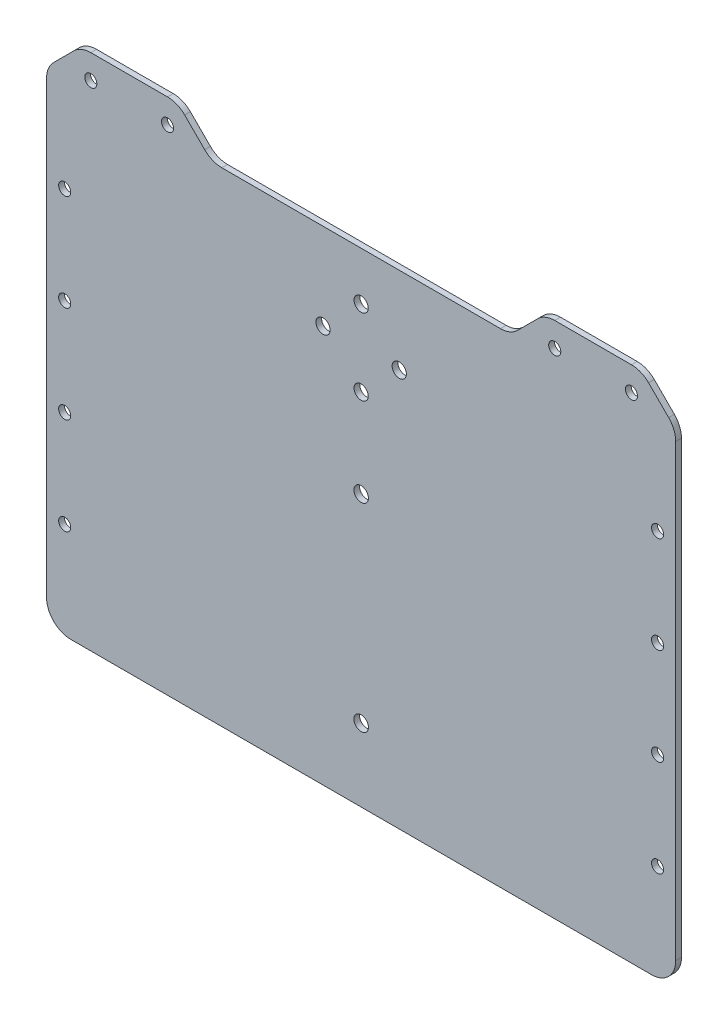
SolidWorks part; units mm, degrees
material "Thornel VCB-20 Carbon Cloth"
ref_plane "Front Plane" through (0, 0, 0) normal (0, 0, 1) x (1, 0, 0)
ref_plane "Top Plane" through (0, 0, 0) normal (0, 1, 0) x (1, 0, 0)
ref_plane "Right Plane" through (0, 0, 0) normal (1, 0, 0) x (0, 0, -1)
sketch "Sketch1" plane through (0, 0, 0) normal (0, 0, 1) x (1, 0, 0)
  line L0 (0, -63.5) -> (0, 63.5) construction
  line L2 (-82.55, 60.8697) -> (-82.55, -57.15)
  line L3 (-76.2, -63.5) -> (76.2, -63.5)
  line L4 (82.55, 60.8697) -> (82.55, -57.15)
  line L5 (-82.55, 63.5) -> (82.55, -63.5) construction
  line L6 (-82.55, -63.5) -> (82.55, 63.5) construction
  line L7 (-80.6901, 65.3599) -> (-75.4296, 70.6204)
  line L8 (-70.9395, 72.4803) -> (-50.8, 72.4803)
  line L9 (-46.3099, 70.6204) -> (-41.0494, 65.3599)
  line L10 (46.3099, 70.6204) -> (41.0494, 65.3599)
  line L11 (70.9395, 72.4803) -> (50.8, 72.4803)
  line L12 (80.6901, 65.3599) -> (75.4296, 70.6204)
  line L13 (-73.5697, 72.4803) -> (-82.55, 72.4803) construction
  line L14 (-82.55, 72.4803) -> (-82.55, 63.5) construction
  line L15 (-36.5592, 63.5) -> (0, 63.5)
  line L16 (0, 63.5) -> (36.5592, 63.5)
  circle A0 centre (-77.7875, -38.1) radius 1.5875
  circle A1 centre (-77.7875, -12.7) radius 1.5875
  circle A2 centre (-77.7875, 12.7) radius 1.5875
  circle A3 centre (-77.7875, 38.1) radius 1.5875
  circle A4 centre (77.7875, 38.1) radius 1.5875
  circle A5 centre (77.7875, 12.7) radius 1.5875
  circle A6 centre (77.7875, -12.7) radius 1.5875
  circle A7 centre (77.7875, -38.1) radius 1.5875
  arc A8 (82.55, 60.8697) -> (80.6901, 65.3599) centre (76.2, 60.8697) ccw
  arc A9 (75.4296, 70.6204) -> (70.9395, 72.4803) centre (70.9395, 66.1303) ccw
  arc A10 (46.3099, 70.6204) -> (50.8, 72.4803) centre (50.8, 66.1303) cw
  arc A11 (41.0494, 65.3599) -> (36.5592, 63.5) centre (36.5592, 69.85) cw
  arc A12 (-36.5592, 63.5) -> (-41.0494, 65.3599) centre (-36.5592, 69.85) cw
  arc A13 (-46.3099, 70.6204) -> (-50.8, 72.4803) centre (-50.8, 66.1303) ccw
  arc A14 (-70.9395, 72.4803) -> (-75.4296, 70.6204) centre (-70.9395, 66.1303) ccw
  arc A15 (-82.55, 60.8697) -> (-80.6901, 65.3599) centre (-76.2, 60.8697) cw
  arc A16 (76.2, -63.5) -> (82.55, -57.15) centre (76.2, -57.15) ccw
  arc A17 (-76.2, -63.5) -> (-82.55, -57.15) centre (-76.2, -57.15) cw
  circle A18 centre (-70.9395, 66.1303) radius 1.5875
  circle A19 centre (-50.8, 66.1303) radius 1.5875
  circle A20 centre (50.8, 66.1303) radius 1.5875
  circle A21 centre (70.9395, 66.1303) radius 1.5875
  point P0 (0, 0)
  point P36 (73.5697, 72.4803)
  point P39 (48.1697, 72.4803)
  point P42 (39.1895, 63.5)
  point P45 (-39.1895, 63.5)
  point P48 (-48.1697, 72.4803)
  dimension "D3" = 3.175
  dimension "D11" = 6.35
  dimension "D12" = 6.35
  dimension "D13" = 3.175
  dimension "D14" = 3.175
  dimension "D1" = 165.1
  dimension "D2" = 127
  dimension "D4" = 25.4
  dimension "D5" = 4.7625
  dimension "D7" = 50.8
  dimension "D8" = 12.7
  dimension "D9" = 135
  dimension "D10" = 25.4
  dimension "D6" = 4
extrude "Boss-Extrude1" add sketch "Sketch1" along normal blind 1.5
sketch "Sketch2" plane through (0, 0, 1.5) normal (0, 0, 1) x (1, 0, 0)
  line L0 (0, -44.45) -> (0, 7.6334) construction
  line L1 (0, -63.5) -> (0, 63.5) construction
  line L3 (-82.55, 1.8599) -> (82.55, 1.8599) construction
  line L4 (-82.55, 60.8697) -> (-82.55, -57.15) construction
  line L5 (82.55, -57.15) -> (82.55, 60.8697) construction
  line L7 (-76.2, -63.5) -> (76.2, -63.5) construction
  circle A0 centre (0, -44.45) radius 1.9062
  circle A1 centre (0, 7.6334) radius 1.9062
  dimension "D2" = 3.8125
  dimension "D3" = 3.8125
  dimension "D1" = 52.0834
  dimension "D4" = 19.05
extrude "Cut-Extrude1" cut sketch "Sketch2" against normal through all
sketch "Sketch3" plane through (0, 0, 1.5) normal (0, 0, 1) x (1, 0, 0)
  line L0 (0, 50.8) -> (0, 30.8) construction
  line L1 (-10, 40.8) -> (10, 40.8) construction
  line L2 (-10, 40.8) -> (0, 50.8) construction
  line L3 (0, 50.8) -> (10, 40.8) construction
  line L4 (10, 40.8) -> (0, 30.8) construction
  line L5 (0, 30.8) -> (-10, 40.8) construction
  line L6 (0, 63.5) -> (0, -63.5) construction
  line L8 (-76.2, -63.5) -> (76.2, -63.5) construction
  circle A0 centre (0, 50.8) radius 1.8669
  circle A1 centre (-10, 40.8) radius 1.8669
  circle A2 centre (0, 30.8) radius 1.8669
  circle A3 centre (10, 40.8) radius 1.8669
  dimension "D1" = 3.7338
  dimension "D2" = 12.7
extrude "Cut-Extrude2" cut sketch "Sketch3" against normal through all
equation "\"Top Plate Width\" = 4.5in"
equation "\"Plate Width\" = 5in"
equation "\"Plate Thickness\" = 0.375in"
equation "\"Num holes\" = 4"
equation "\"Plate Height\" = 1.25in"
equation "\"D2@Sketch1\"=\"Plate Width\""
equation "\"Plate Clearance Hole Diameter\" = 0.125in"
equation "\"D3@Sketch1\"=\"Plate Clearance Hole Diameter\""
equation "\"Hole Spacing\"= \"Plate Width\" / ( \"Num holes\" + 1 )"
equation "\"D5@Sketch1\"=\"Plate Thickness\" / 2"
equation "\"D4@Sketch1\"=\"Hole Spacing\""
equation "\"D7@Sketch1\"= 2 * \"Hole Spacing\""
equation "\"D13@Sketch1\"=\"Plate Clearance Hole Diameter\""
equation "\"D14@Sketch1\"=\"Plate Clearance Hole Diameter\""
equation "\"Plate Tap Hole Diameter\" = 0.116in"
equation "\"Bottom Plate Length\" = 6.5in"
equation "\"D1@Sketch1\"=\"Bottom Plate Length\""
